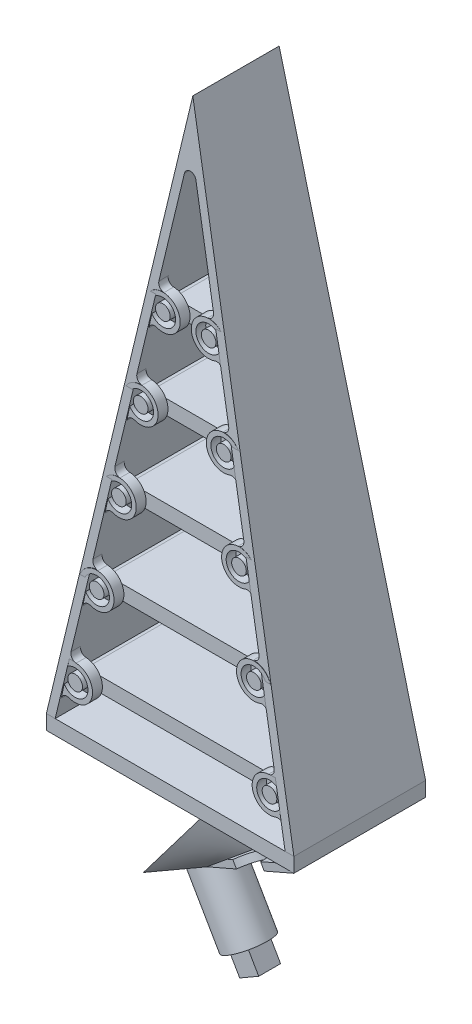
SolidWorks part; units mm, degrees
ref_plane "Ebene vorne" through (0, 0, 0) normal (0, 0, 1) x (1, 0, 0)
ref_plane "Ebene oben" through (0, 0, 0) normal (0, 1, 0) x (1, 0, 0)
ref_plane "Ebene rechts" through (0, 0, 0) normal (1, 0, 0) x (0, 0, -1)
ref_plane "Ebene7" through (0, 0, 9) normal (0, 0, 1) x (1, 0, 0)
ref_plane "Ebene8" through (17, 0, 0) normal (1, 0, 0) x (0, 0, -1)
sketch "Skizze1" plane through (0, 0, 0) normal (0, 0, 1) x (1, 0, 0)
  line L0 (0, 0) -> (16.9111, -80)
  line L1 (16.9111, -80) -> (15.7111, -80)
  line L2 (15.7111, -80) -> (0, -5.6767)
  line L3 (0, -5.6767) -> (-15.7111, -80)
  line L4 (-15.7111, -80) -> (-16.9111, -80)
  line L5 (-16.9111, -80) -> (0, 0)
  point P2 (-16.3111, -80)
  dimension "D1" = 1.2
  dimension "D2" = 1.2
  dimension "D3" = 23.872
  dimension "D4" = 80
extrude "Aufsatz-Linear austragen4" add sketch "Skizze1" along normal blind 18
sketch "Skizze11" plane through (17, 0, 0) normal (1, 0, 0) x (0, 0, -1)
  line L0 (-18, -80) -> (-14.9, 0)
  line L1 (-18, 0) -> (0, 0) construction
  line L2 (-14.9, 0) -> (-18, 0)
  line L3 (-18, 0) -> (-18, -80)
  line L4 (0, -80) -> (-3.1, 0)
  line L5 (-3.1, 0) -> (0, 0)
  line L6 (0, 0) -> (0, -80)
  dimension "D1" = 3.1
  dimension "D2" = 3.1
extrude "Schnitt-Linear austragen1" cut sketch "Skizze11" against normal through all
sketch "Skizze6" plane through (0, 0, 9) normal (0, 0, 1) x (1, 0, 0)
  line L1 (0, -5.6767) -> (-15.7111, -80) construction
  line L2 (15.7111, -80) -> (0, -5.6767) construction
  line L8 (3.1325, -25.6767) -> (-3.1325, -25.6767)
  line L11 (-3.1325, -27.6767) -> (3.1325, -27.6767)
  arc A0 (-3.1325, -25.6767) -> (-3.1325, -27.6767) centre (-3.1325, -26.6767) ccw
  arc A1 (3.1325, -25.6767) -> (3.1325, -27.6767) centre (3.1325, -26.6767) cw
  point P4 (-4.1325, -26.6767)
  point P9 (4.1325, -26.6767)
  dimension "D3" = 0.3
  dimension "D1" = 20
  dimension "D2" = 2
  dimension "D4" = 0.3
extrude "Aufsatz-Linear austragen5" add sketch "Skizze6" along normal blind 5.37 and the other way blind 5.37
sketch "Skizze7" plane through (0, 0, 9) normal (0, 0, 1) x (1, 0, 0)
  line L9 (5.6692, -37.6767) -> (-5.6692, -37.6767)
  line L12 (-5.6692, -39.6767) -> (5.6692, -39.6767)
  line L13 (-3.1325, -27.6767) -> (3.1325, -27.6767) construction
  line L14 (0, -5.6767) -> (-15.7111, -80) construction
  line L15 (15.7111, -80) -> (0, -5.6767) construction
  arc A0 (-5.6692, -37.6767) -> (-5.6692, -39.6767) centre (-5.6692, -38.6767) ccw
  arc A1 (5.6692, -37.6767) -> (5.6692, -39.6767) centre (5.6692, -38.6767) cw
  point P3 (-6.6692, -38.6767)
  point P10 (6.6692, -38.6767)
  dimension "D3" = 0.3
  dimension "D1" = 10
  dimension "D2" = 2
  dimension "D4" = 0.3
extrude "Aufsatz-Linear austragen6" add sketch "Skizze7" along normal blind 5.85 and the other way blind 5.85
sketch "Skizze8" plane through (0, 0, 9) normal (0, 0, 1) x (1, 0, 0)
  line L9 (8.2059, -49.6767) -> (-8.2059, -49.6767)
  line L12 (-8.2059, -51.6767) -> (8.2059, -51.6767)
  line L13 (-5.6692, -39.6767) -> (5.6692, -39.6767) construction
  line L14 (0, -5.6767) -> (-15.7111, -80) construction
  line L15 (15.7111, -80) -> (0, -5.6767) construction
  arc A0 (-8.2059, -49.6767) -> (-8.2059, -51.6767) centre (-8.2059, -50.6767) ccw
  arc A1 (8.2059, -49.6767) -> (8.2059, -51.6767) centre (8.2059, -50.6767) cw
  point P6 (-9.2059, -50.6767)
  point P11 (9.2059, -50.6767)
  dimension "D3" = 0.3
  dimension "D1" = 10
  dimension "D2" = 2
  dimension "D4" = 0.3
extrude "Aufsatz-Linear austragen7" add sketch "Skizze8" along normal blind 6.3 and the other way blind 6.3
sketch "Skizze9" plane through (0, 0, 9) normal (0, 0, 1) x (1, 0, 0)
  line L9 (10.7426, -61.6767) -> (-10.7426, -61.6767)
  line L12 (-10.7426, -63.6767) -> (10.7426, -63.6767)
  line L13 (-8.2059, -51.6767) -> (8.2059, -51.6767) construction
  line L14 (0, -5.6767) -> (-15.7111, -80) construction
  line L15 (15.7111, -80) -> (0, -5.6767) construction
  arc A0 (-10.7426, -61.6767) -> (-10.7426, -63.6767) centre (-10.7426, -62.6767) ccw
  arc A1 (10.7426, -61.6767) -> (10.7426, -63.6767) centre (10.7426, -62.6767) cw
  point P3 (-11.7426, -62.6767)
  point P10 (11.7426, -62.6767)
  dimension "D3" = 0.3
  dimension "D1" = 10
  dimension "D2" = 2
  dimension "D4" = 0.3
extrude "Aufsatz-Linear austragen8" add sketch "Skizze9" along normal blind 6.8 and the other way blind 6.8
sketch "Skizze10" plane through (0, 0, 9) normal (0, 0, 1) x (1, 0, 0)
  line L9 (13.2792, -73.6767) -> (-13.2792, -73.6767)
  line L12 (-13.2792, -75.6767) -> (13.2792, -75.6767)
  line L13 (-10.7426, -63.6767) -> (10.7426, -63.6767) construction
  line L14 (0, -5.6767) -> (-15.7111, -80) construction
  line L15 (15.7111, -80) -> (0, -5.6767) construction
  arc A0 (-13.2792, -73.6767) -> (-13.2792, -75.6767) centre (-13.2792, -74.6767) ccw
  arc A1 (13.2792, -73.6767) -> (13.2792, -75.6767) centre (13.2792, -74.6767) cw
  point P3 (-14.2792, -74.6767)
  point P10 (14.2792, -74.6767)
  dimension "D3" = 0.3
  dimension "D1" = 10
  dimension "D2" = 2
  dimension "D4" = 0.3
extrude "Aufsatz-Linear austragen9" add sketch "Skizze10" along normal blind 7.2 and the other way blind 7.2
sketch "Skizze13" plane through (0, 0, 14.37) normal (0, 0, 1) x (1, 0, 0)
  circle A0 centre (-3.1325, -26.6767) radius 1
  circle A1 centre (3.1325, -26.6767) radius 1
  dimension "D1" = 2
  dimension "D2" = 2
extrude "Aufsatz-Linear austragen12" add sketch "Skizze13" along normal blind 1.5
sketch "Skizze15" plane through (0, 0, 15.3) normal (0, 0, 1) x (1, 0, 0)
  circle A0 centre (-8.2059, -50.6767) radius 1
  circle A1 centre (8.2059, -50.6767) radius 1
extrude "Aufsatz-Linear austragen14" add sketch "Skizze15" along normal blind 1.5
sketch "Skizze14" plane through (0, 0, 14.85) normal (0, 0, 1) x (1, 0, 0)
  circle A0 centre (-5.6692, -38.6767) radius 1
  circle A1 centre (5.6692, -38.6767) radius 1
extrude "Aufsatz-Linear austragen13" add sketch "Skizze14" along normal blind 1.5
sketch "Skizze16" plane through (0, 0, 15.8) normal (0, 0, 1) x (1, 0, 0)
  circle A0 centre (-10.7426, -62.6767) radius 1
  circle A1 centre (10.7426, -62.6767) radius 1
extrude "Aufsatz-Linear austragen15" add sketch "Skizze16" along normal blind 1.5
sketch "Skizze17" plane through (0, 0, 16.2) normal (0, 0, 1) x (1, 0, 0)
  circle A0 centre (-13.2792, -74.6767) radius 1
  circle A1 centre (13.2792, -74.6767) radius 1
extrude "Aufsatz-Linear austragen16" add sketch "Skizze17" along normal blind 1.5
sketch "Skizze18" plane through (0, 0, 3.63) normal (0, 0, -1) x (-1, 0, 0)
  circle A0 centre (-3.1325, -26.6767) radius 1
  circle A1 centre (3.1325, -26.6767) radius 1
extrude "Aufsatz-Linear austragen17" add sketch "Skizze18" along normal blind 1.5
sketch "Skizze19" plane through (0, 0, 3.15) normal (0, 0, -1) x (-1, 0, 0)
  circle A0 centre (-5.6692, -38.6767) radius 1
  circle A1 centre (5.6692, -38.6767) radius 1
extrude "Aufsatz-Linear austragen18" add sketch "Skizze19" along normal blind 1.5
sketch "Skizze20" plane through (0, 0, 2.7) normal (0, 0, -1) x (-1, 0, 0)
  circle A0 centre (-8.2059, -50.6767) radius 1
  circle A1 centre (8.2059, -50.6767) radius 1
extrude "Aufsatz-Linear austragen19" add sketch "Skizze20" along normal blind 1.5
sketch "Skizze21" plane through (0, 0, 2.2) normal (0, 0, -1) x (-1, 0, 0)
  circle A0 centre (-10.7426, -62.6767) radius 1
  circle A1 centre (10.7426, -62.6767) radius 1
extrude "Aufsatz-Linear austragen20" add sketch "Skizze21" along normal blind 1.5
sketch "Skizze22" plane through (0, 0, 1.8) normal (0, 0, -1) x (-1, 0, 0)
  circle A0 centre (-13.2792, -74.6767) radius 1
  circle A1 centre (13.2792, -74.6767) radius 1
extrude "Aufsatz-Linear austragen21" add sketch "Skizze22" along normal blind 1.5
sketch "Skizze24" plane through (0, 0, 15.87) normal (0, 0, 1) x (1, 0, 0)
  circle A0 centre (-3.1325, -26.6767) radius 1.75
  circle A1 centre (-3.1325, -26.6767) radius 2.375
  circle A2 centre (3.1325, -26.6767) radius 1.75
  circle A3 centre (3.1325, -26.6767) radius 2.375
  dimension "D1" = 3.5
  dimension "D2" = 4.75
  dimension "D3" = 3.5
  dimension "D4" = 4.75
extrude "Aufsatz-Linear austragen22" add sketch "Skizze24" against normal blind 1.35
sketch "Skizze25" plane through (0, 0, 16.35) normal (0, 0, 1) x (1, 0, 0)
  circle A0 centre (-5.6692, -38.6767) radius 1.75
  circle A1 centre (-5.6692, -38.6767) radius 2.375
  circle A2 centre (5.6692, -38.6767) radius 1.75
  circle A3 centre (5.6692, -38.6767) radius 2.375
  dimension "D1" = 3.5
  dimension "D2" = 4.75
  dimension "D3" = 3.5
  dimension "D4" = 4.75
extrude "Aufsatz-Linear austragen23" add sketch "Skizze25" against normal blind 1.35
sketch "Skizze26" plane through (0, 0, 16.8) normal (0, 0, 1) x (1, 0, 0)
  circle A0 centre (-8.2059, -50.6767) radius 1.75
  circle A1 centre (-8.2059, -50.6767) radius 2.375
  circle A2 centre (8.2059, -50.6767) radius 1.75
  circle A3 centre (8.2059, -50.6767) radius 2.375
  dimension "D1" = 3.5
  dimension "D2" = 4.75
  dimension "D3" = 3.5
  dimension "D4" = 4.75
extrude "Aufsatz-Linear austragen24" add sketch "Skizze26" against normal blind 1.35
sketch "Skizze27" plane through (0, 0, 17.3) normal (0, 0, 1) x (1, 0, 0)
  circle A0 centre (-10.7426, -62.6767) radius 1.75
  circle A1 centre (-10.7426, -62.6767) radius 2.375
  circle A2 centre (10.7426, -62.6767) radius 1.75
  circle A3 centre (10.7426, -62.6767) radius 2.375
  dimension "D1" = 3.5
  dimension "D2" = 4.75
  dimension "D3" = 3.5
  dimension "D4" = 4.75
extrude "Aufsatz-Linear austragen25" add sketch "Skizze27" against normal blind 1.35
sketch "Skizze28" plane through (0, 0, 17.7) normal (0, 0, 1) x (1, 0, 0)
  circle A0 centre (-13.2792, -74.6767) radius 1.75
  circle A1 centre (-13.2792, -74.6767) radius 2.375
  circle A2 centre (13.2792, -74.6767) radius 1.75
  circle A3 centre (13.2792, -74.6767) radius 2.375
  dimension "D1" = 3.5
  dimension "D2" = 4.75
  dimension "D3" = 3.5
  dimension "D4" = 4.75
extrude "Aufsatz-Linear austragen26" add sketch "Skizze28" against normal blind 1.35
sketch "Skizze29" plane through (0, 0, 2.13) normal (0, 0, -1) x (-1, 0, 0)
  circle A0 centre (-3.1325, -26.6767) radius 1.75
  circle A1 centre (-3.1325, -26.6767) radius 2.375
  circle A2 centre (3.1325, -26.6767) radius 1.75
  circle A3 centre (3.1325, -26.6767) radius 2.375
extrude "Aufsatz-Linear austragen27" add sketch "Skizze29" against normal blind 1.35
sketch "Skizze30" plane through (0, 0, 1.65) normal (0, 0, -1) x (-1, 0, 0)
  circle A0 centre (-5.6692, -38.6767) radius 1.75
  circle A1 centre (-5.6692, -38.6767) radius 2.375
  circle A2 centre (5.6692, -38.6767) radius 1.75
  circle A3 centre (5.6692, -38.6767) radius 2.375
extrude "Aufsatz-Linear austragen28" add sketch "Skizze30" against normal blind 1.35
sketch "Skizze31" plane through (0, 0, 1.2) normal (0, 0, -1) x (-1, 0, 0)
  circle A0 centre (-8.2059, -50.6767) radius 1.75
  circle A1 centre (-8.2059, -50.6767) radius 2.375
  circle A2 centre (8.2059, -50.6767) radius 1.75
  circle A3 centre (8.2059, -50.6767) radius 2.375
extrude "Aufsatz-Linear austragen29" add sketch "Skizze31" against normal blind 1.35
sketch "Skizze32" plane through (0, 0, 0.7) normal (0, 0, -1) x (-1, 0, 0)
  circle A0 centre (-10.7426, -62.6767) radius 1.75
  circle A1 centre (-10.7426, -62.6767) radius 2.375
  circle A2 centre (10.7426, -62.6767) radius 1.75
  circle A3 centre (10.7426, -62.6767) radius 2.375
extrude "Aufsatz-Linear austragen30" add sketch "Skizze32" against normal blind 1.35
sketch "Skizze33" plane through (0, 0, 0.3) normal (0, 0, -1) x (-1, 0, 0)
  circle A0 centre (-13.2792, -74.6767) radius 1.75
  circle A1 centre (-13.2792, -74.6767) radius 2.375
  circle A2 centre (13.2792, -74.6767) radius 1.75
  circle A3 centre (13.2792, -74.6767) radius 2.375
extrude "Aufsatz-Linear austragen31" add sketch "Skizze33" against normal blind 1.35
fillet "Verrundung1" radius 0.8 1 edges at (0, -5.6767, 9)
fillet "Verrundung2" radius 0.8 40 edges at (12.4073, -64.3707, 16.625) (9.8706, -52.3707, 16.125) (7.3339, -40.3707, 15.675) (4.7973, -28.3707, 15.195) (-4.7973, -28.3707, 15.195) (-7.3339, -40.3707, 15.675) (-9.8706, -52.3707, 16.125) (-12.4073, -64.3707, 16.625) (-14.9439, -76.3707, 17.025) (14.9439, -76.3707, 17.025) (14.116, -72.454, 17.025) (-14.116, -72.454, 17.025) (-11.5793, -60.454, 16.5963) (11.5793, -60.454, 16.5963) (9.0427, -48.454, 16.1138) (-9.0427, -48.454, 16.1138) (-6.506, -36.454, 15.6563) (6.506, -36.454, 15.6563) (3.9693, -24.454, 15.1838) (-3.9693, -24.454, 15.1838) (-7.3339, -40.3707, 2.325) (-4.7973, -28.3707, 2.805) (-3.9693, -24.454, 2.8162) (-6.506, -36.454, 2.3437) (-9.0427, -48.454, 1.8862) (-9.8706, -52.3707, 1.875) (-12.4073, -64.3707, 1.375) (-11.5793, -60.454, 1.4037) (-14.116, -72.454, 0.975) (-14.9439, -76.3707, 0.975) (14.9439, -76.3707, 0.975) (14.116, -72.454, 0.975) (12.4073, -64.3707, 1.375) (11.5793, -60.454, 1.4037) (9.8706, -52.3707, 1.875) (9.0427, -48.454, 1.8862) (7.3339, -40.3707, 2.325) (6.506, -36.454, 2.3437) (4.7973, -28.3707, 2.805) (3.9693, -24.454, 2.8162)
sketch "Skizze37" plane through (0, -80, 0) normal (0, -1, 0) x (1, 0, 0)
  line L0 (-16.9111, 0) -> (-15.7111, 0)
  line L1 (-15.7111, 0) -> (16.9111, 0)
  line L2 (16.9111, 0) -> (16.9111, 18)
  line L3 (16.9111, 18) -> (-16.9111, 18)
  line L4 (-16.9111, 18) -> (-16.9111, 0)
extrude "Aufsatz-Linear austragen32" add sketch "Skizze37" along normal blind 2
ref_plane "Ebene9" through (0, 0, 9) normal (0, 0, 1) x (1, 0, 0)
ref_plane "Ebene15" through (39.7348, -68.8227, 0) normal (0.5, -0.866, 0) x (0, 0, 1)
sketch "Skizze68" plane through (0, -82, 0) normal (0, -1, 0) x (1, 0, 0)
  line L0 (11.2943, 0) -> (11.2943, 18)
  line L1 (-16.9111, 0) -> (16.9111, 0) construction
  line L2 (16.9111, 18) -> (-16.9111, 18) construction
  line L3 (11.2943, 18) -> (4.0769, 18)
  line L4 (4.0769, 18) -> (4.0769, 0)
  line L5 (4.0769, 0) -> (11.2943, 0)
sketch "Skizze69" plane through (39.7348, -68.8227, 0) normal (0.5, -0.866, 0) x (0, 0, 1)
  line L0 (4, 54.7108) -> (4, 44.7108)
  line L1 (14, 44.7108) -> (14, 54.7108)
  line L2 (14, 54.7108) -> (4, 54.7108)
  line L3 (4, 44.7108) -> (14, 44.7108)
  line L4 (9, -1.1) -> (9, 1.1) construction
  point P0 (9, 44.7108)
loft "Ausformung5" add profiles "Skizze68", "Skizze69" connector at (11.2943, -82, 0) connector at (1.0141, -91.1781, 4)
sketch "Skizze71" plane through (39.7348, -68.8227, 0) normal (0.5, -0.866, 0) x (-0.866, -0.5, 0)
  line L0 (-1.1058, -9) -> (1.1058, -9) construction
  circle A0 centre (49.6554, -9) radius 3
  point P2 (0, 0)
  point P5 (49.6554, -9)
extrude "Aufsatz-Linear austragen39" add sketch "Skizze71" along normal blind 10
sketch "Skizze72" plane through (39.7348, -68.8227, 0) normal (0.5, -0.866, 0) x (0, 0, 1)
  line L0 (18, 26.3545) -> (14, 44.7108)
  line L1 (14, 44.7108) -> (4, 44.7108)
  line L2 (4, 44.7108) -> (0, 26.3545)
  line L3 (0, 26.3545) -> (18, 26.3545)
extrude "Aufsatz-Linear austragen40" add sketch "Skizze72" against normal blind 1
sketch "Skizze75" plane through (44.7348, -77.483, 0) normal (0.5, -0.866, 0) x (0.866, 0.5, 0)
  line L0 (-49.6388, 8.95) -> (-45.5622, 8.95) construction
  line L1 (-45.5622, 8.95) -> (-53.3014, 8.95) construction
  line L2 (-49.6388, 8.95) -> (-49.6388, 4.2105) construction
  line L3 (-49.6388, 8.95) -> (-49.6388, 14.5367) construction
  line L4 (-51.1388, 7.45) -> (-48.1388, 7.45)
  line L5 (-49.6388, 10.4398) -> (-51.1388, 10.4398)
  line L6 (-51.1388, 10.4398) -> (-51.1388, 7.45)
  line L7 (-48.1388, 7.45) -> (-48.1388, 10.4398)
  line L8 (-48.1388, 10.4398) -> (-49.6388, 10.4398)
extrude "Aufsatz-Linear austragen41" add sketch "Skizze75" along normal blind 3
sketch "Skizze76" plane through (46.2348, -80.0811, 0) normal (0.5, -0.866, 0) x (0.866, 0.5, 0)
  line L0 (-51.1388, 10.4398) -> (-51.1388, 7.45) construction
  line L2 (-51.1388, 7.45) -> (-48.1388, 7.45) construction
  circle A0 centre (-49.6388, 8.95) radius 1
  dimension "D1" = 1.5
  dimension "D2" = 1.5
extrude "Schnitt-Linear austragen4" cut sketch "Skizze76" against normal blind 23
sketch "Skizze77" plane through (39.7348, -68.8227, 0) normal (0.5, -0.866, 0) x (0.866, 0.5, 0)
  line L0 (-35.5327, 2) -> (-32.6052, 1.3621)
  line L1 (-44.7108, 4) -> (-26.3545, 0) construction
  line L2 (-35.5327, 2) -> (-38.4639, 2.6387)
  line L3 (-35.5327, 16) -> (-38.4639, 15.3613)
  line L4 (-26.3545, 18) -> (-44.7108, 14) construction
  line L5 (-38.4639, 15.3613) -> (-32.612, 16.6364)
  arc A0 (-38.4639, 2.6387) -> (-32.6052, 1.3621) centre (-35.6186, 1.6148) cw
  arc A1 (-32.612, 16.6364) -> (-38.4639, 15.3613) centre (-35.6219, 16.3841) cw
  line M4 (-44.7108, 4) -> (-26.3545, 0)
  line M6 (-26.3545, 18) -> (-44.7108, 14)
extrude "Schnitt-Linear austragen5" cut sketch "Skizze77" against normal blind 1 contours A1 M6 | A0 M4 region at (9.1647, -86.4724, 3.0796) region at (9.1615, -86.4743, 14.9209)
sketch "Skizze78" plane through (0, -82, 0) normal (0, -1, 0) x (1, 0, 0)
  line L0 (1.1058, 9) -> (-1.1058, 9) construction
  circle A0 centre (-13.6144, 9) radius 0.5
  point P2 (0, 0)
  point P5 (-13.6144, 9)
extrude "Schnitt-Linear austragen6" cut sketch "Skizze78" against normal up to next (2 mm away) contours A0
